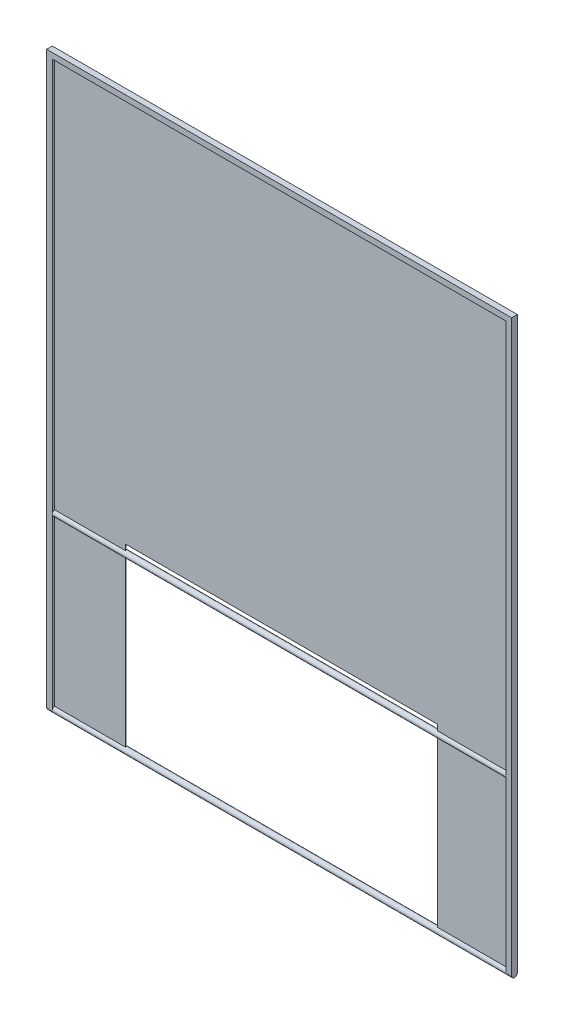
SolidWorks part; units mm, degrees
ref_plane "Front Plane" through (0, 0, 0) normal (0, 0, 1) x (1, 0, 0)
ref_plane "Top Plane" through (0, 0, 0) normal (0, 1, 0) x (1, 0, 0)
ref_plane "Right Plane" through (0, 0, 0) normal (1, 0, 0) x (0, 0, -1)
sketch "Sketch14" plane through (0, 0, 0) normal (0, 0, 1) x (1, 0, 0)
  line L0 (-400, 0) -> (400, 0)
  line L1 (-400, 300) -> (400, 300)
  point P5 (0, 0)
  dimension "D1" = 800
  dimension "D2" = 400
  dimension "D3" = 300
sweep "Sweep2" add path "Sketch14" circular profile diameter 10 parameters "D3"=10
sweep "Sweep3" add path "Sketch14<3>" circular profile diameter 10 parameters "D3"=10
sketch "Sketch14<3>" plane through (0, 0, 0) normal (0, 0, 1) x (1, 0, 0) same geometry as "Sketch14"
sketch "Sketch31" plane through (0, 0, 0) normal (0, 0, 1) x (1, 0, 0)
  line L0 (400, -5) -> (400, 995)
  line L1 (400, 995) -> (-400, 995)
  line L2 (-400, 995) -> (-400, -5)
  dimension "D1" = 800
  dimension "D2" = 1000
extrude "Extrude-Thin2" add sketch "Sketch31" along normal mid plane 10 thin thin type one direction wall 10
fillet "Fillet4" radius 5 4 edges at (405, -5, -5) (405, -5, 5) (-410, -5, 0) (-405, -5, 5)
sketch "Sketch32" plane through (0, 0, 0) normal (0, 0, 1) x (1, 0, 0)
  line L0 (275, 0) -> (275, 315)
  line L1 (410, 0) -> (275, 0)
  line L2 (410, 0) -> (410, 1005)
  line L3 (410, 1005) -> (-410, 1005)
  line L4 (-410, 0) -> (-410, 1005)
  line L6 (275, 315) -> (-275, 315)
  line L7 (-275, 315) -> (-275, 0)
  line L8 (-275, 0) -> (-410, 0)
  dimension "D1" = 550
  dimension "D2" = 275
  dimension "D3" = 315
extrude "Boss-Extrude1" add sketch "Sketch32" along normal blind 1 contours L1 L0 L6 L7 L8 L4 L3 L2
